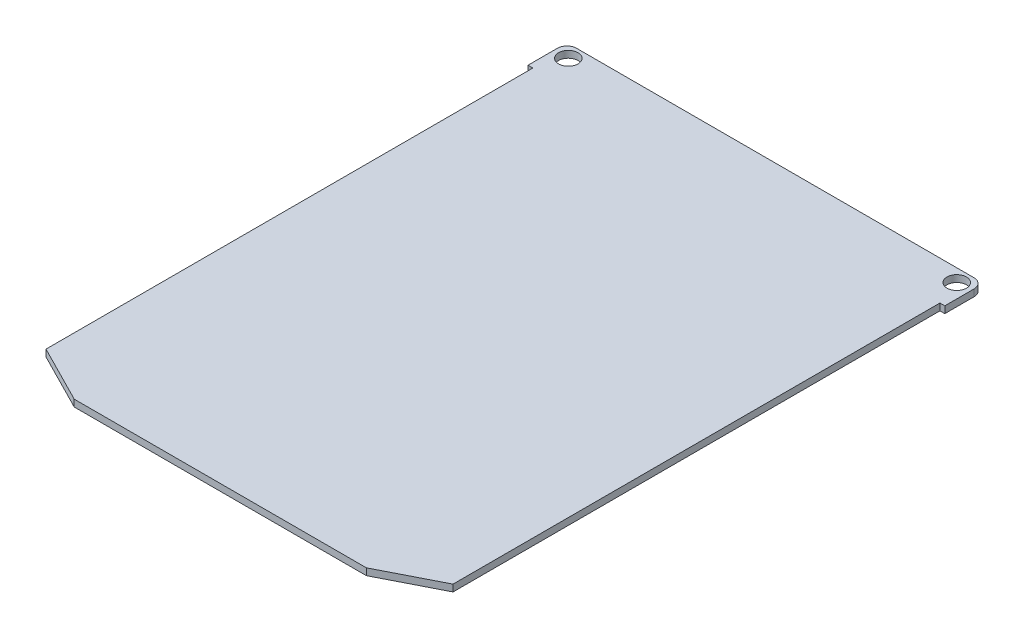
SolidWorks part; units mm, degrees
ref_plane "Front Plane" through (0, 0, 0) normal (0, 0, 1) x (1, 0, 0)
ref_plane "Top Plane" through (0, 0, 0) normal (0, 1, 0) x (1, 0, 0)
ref_plane "Right Plane" through (0, 0, 0) normal (1, 0, 0) x (0, 0, -1)
sketch "Sketch1" plane through (0, 0, 0) normal (0, 1, 0) x (1, 0, 0)
  line L0 (-21.4, 26.5) -> (-20.9, 26.5)
  line L3 (-21.4, 29.5) -> (-21.4, 26.5)
  line L11 (-20.4, 30.5) -> (20.4, 30.5)
  line L17 (0, 30.5) -> (0, -30.5) construction
  line L21 (21.4, 29.5) -> (21.4, 26.5)
  line L22 (21.4, 26.5) -> (20.9, 26.5)
  line L23 (-20.9, 26.5) -> (-20.9, -23.5)
  line L24 (-20.9, -23.5) -> (20.9, -23.5) construction
  line L25 (20.9, -23.5) -> (20.9, 26.5)
  line L26 (-15, -26.5) -> (15, -26.5)
  line L29 (-20.9, -23.5) -> (-15, -26.5)
  line L30 (15, -26.5) -> (20.9, -23.5)
  arc A1 (-21.4, 29.5) -> (-20.4, 30.5) centre (-20.4, 29.5) cw
  circle A6 centre (-19.9444, 29.1814) radius 1
  circle A8 centre (19.9444, 29.1814) radius 1
  arc A10 (21.4, 29.5) -> (20.4, 30.5) centre (20.4, 29.5) ccw
  point P4 (-33.4108, 22.2153)
  point P17 (0, 0)
  point P18 (0, 0)
  point P19 (0, -26.5)
  point P22 (-19.9444, 29.1814)
  dimension "D6" = 30.5
  dimension "D9" = 40.8
  dimension "D3" = 29.1814
  dimension "D5" = 1
  dimension "D2" = 19.9444
  dimension "D12" = 2
  dimension "D4" = 50
  dimension "D7" = 35.9
  dimension "D8" = 3
  dimension "D10" = 26.5
  dimension "D11" = 20.9
extrude "Boss-Extrude1" add sketch "Sketch1" along normal blind 0.7
